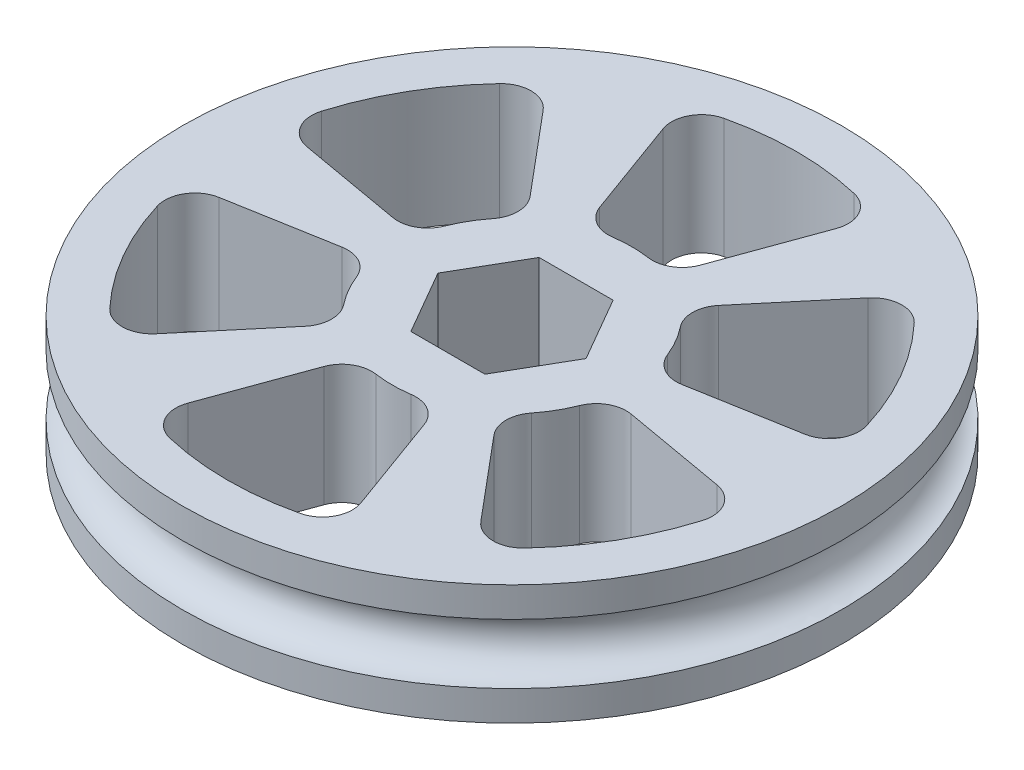
SolidWorks part; units mm, degrees
ref_plane "Front" through (0, 0, 0) normal (0, 0, 1) x (1, 0, 0)
ref_plane "Top" through (0, 0, 0) normal (0, 1, 0) x (1, 0, 0)
ref_plane "Right" through (0, 0, 0) normal (1, 0, 0) x (0, 0, -1)
sketch "Sketch1" plane through (0, 0, 0) normal (0, 1, 0) x (1, 0, 0)
  line L1 (7.8456, 0) -> (3.9228, 6.7945)
  line L2 (3.9228, 6.7945) -> (-3.9228, 6.7945)
  line L3 (-3.9228, 6.7945) -> (-7.8456, 0)
  line L4 (-7.8456, 0) -> (-3.9228, -6.7945)
  line L5 (-3.9228, -6.7945) -> (3.9228, -6.7945)
  line L6 (3.9228, -6.7945) -> (7.8456, 0)
  circle A0 centre (0, 0) radius 6.7945 construction
  circle A1 centre (0, 0) radius 34.925
  dimension "D1" = 69.85
extrude "Boss-Extrude1" add sketch "Sketch1" along normal blind 12.7
ref_plane "Mid_Plane" through (0, 6.35, 0) normal (0, -1, 0) x (-1, 0, 0)
sketch "Sketch4" plane through (-6.35, 6.35, 0) normal (0, 0, -1) x (0, 1, 0)
  line L0 (-6.35, 6.35) -> (-6.35, 41.275) construction
  line L1 (-6.35, 41.275) -> (0, 41.275) construction
  line L3 (6.35, 41.275) -> (-6.35, 41.275) construction
  line L4 (0, 41.275) -> (6.35, 41.275) construction
  line L5 (-6.35, 41.275) -> (-6.35, -28.575) construction
  circle A1 centre (0, 41.275) radius 3.175
  dimension "D3" = 6.35
ref_axis "Axis1" through (0, 12.7, 0) along (0, -1, 0)
revolve "Cut-Revolve1" cut sketch "Sketch4" angle 360 about axis through (0, 12.7, 0) along (0, -1, 0)
sketch "Sketch5" plane through (0, 0, 0) normal (0, -1, 0) x (1, 0, 0)
  line L0 (5.3199, 14.6162) -> (9.1662, 25.1838)
  line L1 (-5.3199, 14.6162) -> (-9.1662, 25.1838)
  line L2 (0, 0) -> (0, 30.1625) construction
  line L3 (15.318, 2.701) -> (26.3929, 4.6538)
  line L4 (9.9981, 11.9153) -> (17.2268, 20.5301)
  line L5 (9.9981, -11.9153) -> (17.2268, -20.5301)
  line L6 (15.318, -2.701) -> (26.3929, -4.6538)
  line L7 (-5.3199, -14.6162) -> (-9.1662, -25.1838)
  line L8 (5.3199, -14.6162) -> (9.1662, -25.1838)
  line L9 (-15.318, -2.701) -> (-26.3929, -4.6538)
  line L10 (-9.9981, -11.9153) -> (-17.2268, -20.5301)
  line L11 (-9.9981, 11.9153) -> (-17.2268, 20.5301)
  line L12 (-15.318, 2.701) -> (-26.3929, 4.6538)
  arc A0 (6.91, 29.3603) -> (-6.91, 29.3603) centre (0, 0) ccw
  arc A1 (1.8691, 12.5617) -> (-1.8691, 12.5617) centre (0, 0) ccw
  arc A2 (-1.8691, 12.5617) -> (-5.3199, 14.6162) centre (-2.3363, 15.7021) cw
  arc A3 (1.8691, 12.5617) -> (5.3199, 14.6162) centre (2.3363, 15.7021) ccw
  arc A4 (9.1662, 25.1838) -> (6.91, 29.3603) centre (6.1826, 26.2698) ccw
  arc A5 (-9.1662, 25.1838) -> (-6.91, 29.3603) centre (-6.1826, 26.2698) cw
  arc A6 (28.8818, 8.6959) -> (21.9718, 20.6644) centre (0, 0) ccw
  arc A7 (11.8133, 4.6622) -> (9.9442, 7.8995) centre (0, 0) ccw
  arc A8 (9.9442, 7.8995) -> (9.9981, 11.9153) centre (12.4303, 9.8744) cw
  arc A9 (11.8133, 4.6622) -> (15.318, 2.701) centre (14.7666, 5.8277) ccw
  arc A10 (26.3929, 4.6538) -> (28.8818, 8.6959) centre (25.8416, 7.7806) ccw
  arc A11 (17.2268, 20.5301) -> (21.9718, 20.6644) centre (19.659, 18.4892) cw
  arc A12 (21.9718, -20.6644) -> (28.8818, -8.6959) centre (0, 0) ccw
  arc A13 (9.9442, -7.8995) -> (11.8133, -4.6622) centre (0, 0) ccw
  arc A14 (11.8133, -4.6622) -> (15.318, -2.701) centre (14.7666, -5.8277) cw
  arc A15 (9.9442, -7.8995) -> (9.9981, -11.9153) centre (12.4303, -9.8744) ccw
  arc A16 (17.2268, -20.5301) -> (21.9718, -20.6644) centre (19.659, -18.4892) ccw
  arc A17 (26.3929, -4.6538) -> (28.8818, -8.6959) centre (25.8416, -7.7806) cw
  arc A18 (-6.91, -29.3603) -> (6.91, -29.3603) centre (0, 0) ccw
  arc A19 (-1.8691, -12.5617) -> (1.8691, -12.5617) centre (0, 0) ccw
  arc A20 (1.8691, -12.5617) -> (5.3199, -14.6162) centre (2.3363, -15.7021) cw
  arc A21 (-1.8691, -12.5617) -> (-5.3199, -14.6162) centre (-2.3363, -15.7021) ccw
  arc A22 (-9.1662, -25.1838) -> (-6.91, -29.3603) centre (-6.1826, -26.2698) ccw
  arc A23 (9.1662, -25.1838) -> (6.91, -29.3603) centre (6.1826, -26.2698) cw
  arc A24 (-28.8818, -8.6959) -> (-21.9718, -20.6644) centre (0, 0) ccw
  arc A25 (-11.8133, -4.6622) -> (-9.9442, -7.8995) centre (0, 0) ccw
  arc A26 (-9.9442, -7.8995) -> (-9.9981, -11.9153) centre (-12.4303, -9.8744) cw
  arc A27 (-11.8133, -4.6622) -> (-15.318, -2.701) centre (-14.7666, -5.8277) ccw
  arc A28 (-26.3929, -4.6538) -> (-28.8818, -8.6959) centre (-25.8416, -7.7806) ccw
  arc A29 (-17.2268, -20.5301) -> (-21.9718, -20.6644) centre (-19.659, -18.4892) cw
  arc A30 (-21.9718, 20.6644) -> (-28.8818, 8.6959) centre (0, 0) ccw
  arc A31 (-9.9442, 7.8995) -> (-11.8133, 4.6622) centre (0, 0) ccw
  arc A32 (-11.8133, 4.6622) -> (-15.318, 2.701) centre (-14.7666, 5.8277) cw
  arc A33 (-9.9442, 7.8995) -> (-9.9981, 11.9153) centre (-12.4303, 9.8744) ccw
  arc A34 (-17.2268, 20.5301) -> (-21.9718, 20.6644) centre (-19.659, 18.4892) ccw
  arc A35 (-26.3929, 4.6538) -> (-28.8818, 8.6959) centre (-25.8416, 7.7806) cw
  point P77 (0, 0)
  dimension "D1" = 60.325
  dimension "D2" = 25.4
  dimension "D5" = 3.175
  dimension "D3" = 20
  dimension "D4" = 20
  dimension "D6" = 6
extrude "Cut-Extrude1" cut sketch "Sketch5" against normal through all
